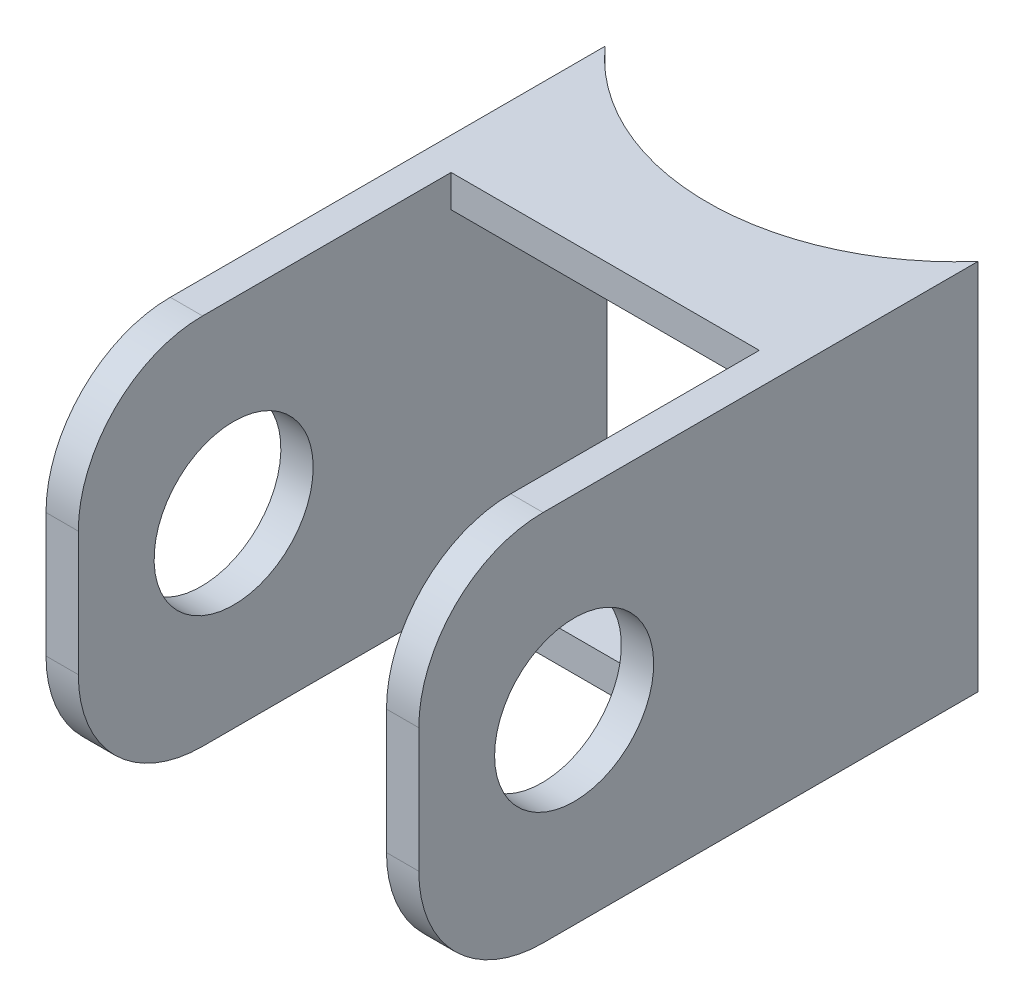
SolidWorks part; units mm, degrees
material "AISI 4130 Steel, annealed at 865C"
ref_plane "Front Plane" through (0, 0, 0) normal (0, 0, 1) x (1, 0, 0)
ref_plane "Top Plane" through (0, 0, 0) normal (0, 1, 0) x (1, 0, 0)
ref_plane "Right Plane" through (0, 0, 0) normal (1, 0, 0) x (0, 0, -1)
sketch "Sketch1" plane through (0, 0, 0) normal (0, 0, 1) x (1, 0, 0)
  line L1 (-9.525, 9.525) -> (9.525, 9.525)
  line L2 (-9.525, 9.525) -> (-9.525, -9.525)
  line L3 (-9.525, -9.525) -> (9.525, -9.525)
  line L4 (9.525, 9.525) -> (9.525, -9.525)
  line L5 (-9.525, 9.525) -> (9.525, -9.525) construction
  line L6 (-9.525, -9.525) -> (9.525, 9.525) construction
  line L7 (-7.874, 7.874) -> (7.874, 7.874)
  line L8 (-7.874, 7.874) -> (-7.874, -7.874)
  line L9 (-7.874, -7.874) -> (7.874, -7.874)
  line L10 (7.874, 7.874) -> (7.874, -7.874)
  line L11 (-7.874, 7.874) -> (7.874, -7.874) construction
  line L12 (-7.874, -7.874) -> (7.874, 7.874) construction
  point P0 (0, 0)
  point P6 (0, 0)
  dimension "D1" = 19.05
  dimension "D2" = 1.651
extrude "Boss-Extrude1" add sketch "Sketch1" along normal blind 28.575
sketch "Sketch5" plane through (0, 9.525, 0) normal (0, 1, 0) x (1, 0, 0)
  line L0 (0, -1000) -> (0, 49000) construction
  circle A0 centre (0, 8.4003) radius 12.7
  dimension "D1" = 25.4
extrude "Cut-Extrude5" cut sketch "Sketch5" against normal through all both and the other way through all
sketch "Sketch3" plane through (9.525, 0, 0) normal (1, 0, 0) x (0, 0, -1)
  line L0 (-28.575, -9.525) -> (0, -9.525) construction
  line L1 (-28.575, 9.525) -> (-20.6375, 9.525) construction
  line L2 (-28.575, 9.525) -> (-28.575, -9.525) construction
  line L3 (-28.575, -9.525) -> (-20.6375, -9.525) construction
  line L4 (-20.6375, 9.525) -> (-20.6375, -9.525) construction
  line L5 (-24.6062, -9.525) -> (-24.6062, 9.525) construction
  line L6 (-28.575, 0) -> (-20.6375, 0) construction
  circle A0 centre (-20.6375, 0) radius 4.064
  point P168 (-24.6062, 0)
  dimension "D1" = 8.128
  dimension "D2" = 7.9375
extrude "Cut-Extrude2" cut sketch "Sketch3" against normal through all both and the other way through all
sketch "Sketch4" plane through (0, -9.525, 0) normal (0, -1, 0) x (1, 0, 0)
  line L1 (-7.874, 28.575) -> (7.874, 28.575)
  line L2 (-7.874, 28.575) -> (-7.874, 9.525)
  line L3 (-7.874, 9.525) -> (7.874, 9.525)
  line L4 (7.874, 28.575) -> (7.874, 9.525)
  line L5 (0, 9.525) -> (0, 28.575) construction
  line L6 (-7.874, 19.05) -> (7.874, 19.05) construction
  line L7 (7.874, 24.7015) -> (7.874, 16.5735) construction
  point P96 (0, 19.05)
  dimension "D1" = 19.05
extrude "Cut-Extrude4" cut sketch "Sketch4" against normal through all both and the other way through all
fillet "Fillet2" radius 6.35 4 edges at (-8.6995, 9.525, 28.575) (8.6995, 9.525, 28.575) (-8.6995, -9.525, 28.575) (8.6995, -9.525, 28.575)
ref_axis "Axis2" through (-9.525, 0, 20.6375) along (1, 0, 0)
ref_point "Point2"
ref_axis "Axis3" through (0, 0, 0) along (0, 0, 1)
sketch "Sketch6" plane through (-9.525, 0, 0) normal (-1, 0, 0) x (0, 0, 1)
  line L0 (28.575, -9.525) -> (20.6375, -9.525) construction
  line L1 (20.6375, 9.525) -> (20.6375, -9.525) construction
  line L2 (24.6062, -9.525) -> (24.6062, 9.525) construction
  line L3 (28.575, 0) -> (20.6375, 0) construction
  line L4 (28.575, 9.525) -> (28.575, -9.525) construction
  line L5 (28.575, 9.525) -> (20.6375, 9.525) construction
  line L6 (28.575, -9.525) -> (20.6375, -9.525)
  line L7 (20.6375, 9.525) -> (20.6375, -9.525)
  line L8 (24.6062, -9.525) -> (24.6062, 9.525)
  line L9 (28.575, 0) -> (20.6375, 0)
  line L10 (28.575, 9.525) -> (28.575, -9.525)
  line L11 (28.575, 9.525) -> (20.6375, 9.525)
  circle A1 centre (20.6375, 0) radius 4.064
  circle A2 centre (20.6375, 0) radius 4.064
  dimension "D1" = 0
sketch3d "3DSketch1"
  line L0 (-387.2527, 0, 64.1994) -> (-405.8026, 0, 68.5356) construction
  line L1 (9.525, 0, 20.6375) -> (-9.525, 0, 20.6375) construction
  line L2 (9.525, 0, 20.6375) -> (19.05, 0, 20.6375) construction
